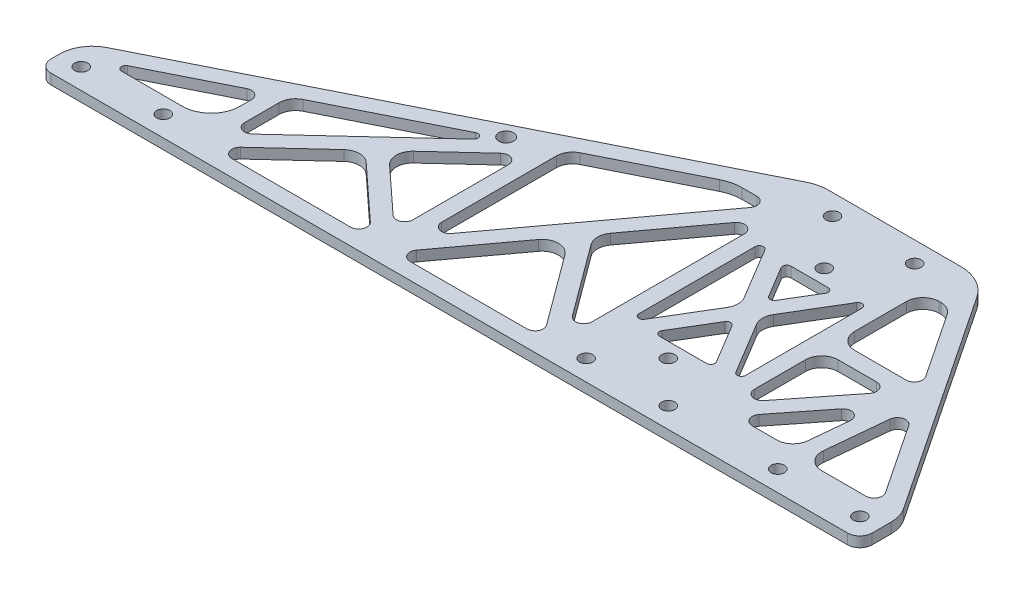
SolidWorks part; units mm, degrees
ref_plane "Front Plane" through (0, 0, 0) normal (0, 0, 1) x (1, 0, 0)
ref_plane "Top Plane" through (0, 0, 0) normal (0, 1, 0) x (1, 0, 0)
ref_plane "Right Plane" through (0, 0, 0) normal (1, 0, 0) x (0, 0, -1)
sketch "Sketch1" plane through (0, 0, 0) normal (0, 1, 0) x (1, 0, 0)
  line L0 (0, 0) -> (254, 0)
  line L2 (203.2, 88.9) -> (152.4, 88.9)
  line L4 (0, 0) -> (0, 12.7)
  line L5 (0, 12.7) -> (152.4, 88.9)
  line L6 (203.2, 88.9) -> (254, 12.7)
  line L7 (254, 12.7) -> (254, 0)
  line L8 (0, 6.35) -> (44.45, 6.35) construction
  line L9 (254, 6.35) -> (222.25, 6.35) construction
  line L10 (139.7, 82.55) -> (207.4333, 82.55) construction
  line L11 (44.45, 0) -> (44.45, 34.925) construction
  line L12 (156.6333, 12.7) -> (154.0933, 7.62)
  line L13 (224.7006, 47.4909) -> (221.314, 12.7) construction
  line L20 (127, 76.2) -> (211.6667, 76.2)
  line L21 (154.0933, 76.2) -> (101.6, 5.08) construction
  line L22 (154.0933, 12.7) -> (154.0933, 7.62)
  line L23 (247.8946, 12.7) -> (194.7333, 12.7)
  line L24 (224.7006, 47.4909) -> (197.2733, 12.7) construction
  line L28 (224.7006, 47.4909) -> (194.7333, 47.4909) construction
  line L31 (5.08, 9.5604) -> (153.5992, 83.82)
  line L32 (200.4813, 83.82) -> (153.5992, 83.82)
  line L33 (200.4813, 83.82) -> (248.92, 11.1619)
  line L34 (248.92, 11.1619) -> (248.92, 5.08)
  line L35 (5.08, 5.08) -> (248.92, 5.08)
  line L36 (5.08, 5.08) -> (5.08, 9.5604)
  line L37 (101.6, 5.08) -> (101.6, 57.8204) construction
  line L39 (127.8467, 40.64) -> (154.0933, 5.08) construction
  line L40 (101.6, 57.8204) -> (44.45, 5.08) construction
  line L41 (73.025, 31.4502) -> (101.6, 5.08) construction
  line L42 (154.0933, 7.62) -> (154.0933, 5.08)
  line L83 (152.8233, 5.08) -> (150.2833, 0)
  line L84 (125.803, 39.1316) -> (152.0497, 3.5716)
  line L107 (152.0497, 77.7084) -> (99.5564, 6.5884)
  line L108 (156.6333, 76.2) -> (194.7333, 12.7) construction
  line L113 (194.7333, 76.2) -> (156.6333, 12.7) construction
  line L117 (104.14, 5.08) -> (104.14, 63.6207)
  line L118 (156.6333, 12.7) -> (194.7333, 12.7)
  line L119 (194.7333, 12.7) -> (201.0833, 0)
  line L120 (154.0933, 6.35) -> (197.9083, 6.35) construction
  line L126 (192.5553, 77.5068) -> (154.4553, 14.0068)
  line L127 (154.4553, 74.8932) -> (192.5553, 11.3932)
  line L128 (156.6333, 12.7) -> (156.6333, 76.2) construction
  line L129 (194.7333, 12.7) -> (194.7333, 76.2) construction
  line L130 (197.2733, 12.7) -> (197.2733, 76.2)
  line L131 (159.1733, 12.7) -> (159.1733, 76.2)
  line L132 (192.1933, 12.7) -> (192.1933, 76.2)
  line L133 (154.0933, 12.7) -> (154.0933, 76.2)
  line L147 (196.9114, 74.8932) -> (158.8114, 11.3932)
  line L148 (158.8114, 77.5068) -> (196.9114, 14.0068)
  line L154 (104.14, 63.6207) -> (42.7274, 6.9466)
  line L155 (71.3024, 29.5836) -> (99.8774, 3.2134)
  line L156 (224.7006, 50.0309) -> (194.7333, 50.0309)
  line L157 (222.7059, 49.0635) -> (195.2786, 14.2725)
  line L158 (197.2733, 12.7) -> (197.2733, 7.62)
  line L159 (222.1726, 47.737) -> (218.7859, 12.9461)
  line L160 (129.8903, 42.1484) -> (156.137, 6.5884)
  line L163 (156.137, 74.6916) -> (103.6436, 3.5716)
  line L164 (99.06, 5.08) -> (99.06, 52.0201)
  line L165 (99.06, 52.0201) -> (46.1726, 3.2134)
  line L166 (175.6833, 19.05) -> (162.9833, 6.35) construction
  line L167 (175.6833, 19.05) -> (188.3833, 6.35) construction
  line L168 (162.9833, 82.55) -> (175.6833, 67.31) construction
  line L169 (175.6833, 67.31) -> (188.3833, 82.55) construction
  line L170 (161.6625, 21.082) -> (189.7041, 21.082) construction
  line L171 (161.6625, 23.622) -> (189.7041, 23.622)
  line L172 (163.1865, 65.278) -> (188.1801, 65.278) construction
  line L173 (163.1865, 62.738) -> (188.1801, 62.738)
  line L174 (74.7476, 33.3168) -> (103.3226, 6.9466)
  line L175 (224.7006, 44.9509) -> (194.7333, 44.9509)
  line L176 (226.6953, 45.9184) -> (199.268, 11.1275)
  line L177 (227.2287, 47.2449) -> (223.842, 12.4539)
  line L178 (8.8192, 11.43) -> (44.45, 11.43)
  line L179 (46.99, 0) -> (46.99, 34.925)
  line L180 (41.91, 0) -> (41.91, 34.925)
  line L181 (198.2745, 13.97) -> (221.4376, 13.97)
  circle A0 centre (6.7733, 6.35) radius 2.032
  circle A1 centre (32.1733, 6.35) radius 2.032
  circle A2 centre (222.25, 6.35) radius 2.032
  circle A3 centre (247.65, 6.35) radius 2.032
  circle A4 centre (162.9833, 82.55) radius 2.032
  circle A5 centre (188.3833, 82.55) radius 2.032
  circle A28 centre (162.9833, 6.35) radius 2.032
  circle A29 centre (188.3833, 6.35) radius 2.032
  arc A32 (197.2733, 12.7) -> (192.1933, 12.7) centre (194.7333, 12.7) cw
  arc A33 (197.2733, 76.2) -> (192.1933, 76.2) centre (194.7333, 76.2) ccw
  arc A34 (159.1733, 12.7) -> (154.0933, 12.7) centre (156.6333, 12.7) cw
  arc A35 (159.1733, 76.2) -> (154.0933, 76.2) centre (156.6333, 76.2) ccw
  arc A45 (192.5553, 77.5068) -> (196.9114, 74.8932) centre (194.7333, 76.2) cw
  arc A46 (154.4553, 14.0068) -> (158.8114, 11.3932) centre (156.6333, 12.7) ccw
  arc A47 (154.4553, 74.8932) -> (158.8114, 77.5068) centre (156.6333, 76.2) cw
  arc A48 (192.5553, 11.3932) -> (196.9114, 14.0068) centre (194.7333, 12.7) ccw
  circle A59 centre (175.6833, 19.05) radius 2.032
  circle A60 centre (175.6833, 67.31) radius 2.032
  arc A61 (125.803, 39.1316) -> (129.8903, 42.1484) centre (127.8467, 40.64) cw
  arc A62 (152.0497, 3.5716) -> (156.137, 6.5884) centre (154.0933, 5.08) ccw
  arc A63 (152.0497, 77.7084) -> (156.137, 74.6916) centre (154.0933, 76.2) cw
  arc A64 (99.5564, 6.5884) -> (103.6436, 3.5716) centre (101.6, 5.08) ccw
  arc A65 (104.14, 5.08) -> (99.06, 5.08) centre (101.6, 5.08) cw
  arc A66 (42.7274, 6.9466) -> (46.1726, 3.2134) centre (44.45, 5.08) ccw
  arc A67 (71.3024, 29.5836) -> (74.7476, 33.3168) centre (73.025, 31.4502) cw
  arc A68 (99.8774, 3.2134) -> (103.3226, 6.9466) centre (101.6, 5.08) ccw
  arc A69 (224.7006, 50.0309) -> (224.7006, 44.9509) centre (224.7006, 47.4909) cw
  arc A70 (194.7333, 50.0309) -> (194.7333, 44.9509) centre (194.7333, 47.4909) ccw
  arc A71 (222.7059, 49.0635) -> (226.6953, 45.9184) centre (224.7006, 47.4909) cw
  arc A72 (195.2786, 14.2725) -> (199.268, 11.1275) centre (197.2733, 12.7) ccw
  arc A73 (222.1726, 47.737) -> (227.2287, 47.2449) centre (224.7006, 47.4909) cw
  arc A74 (218.7859, 12.9461) -> (223.842, 12.4539) centre (221.314, 12.7) ccw
  arc A75 (46.99, 0) -> (41.91, 0) centre (44.45, 0) cw
  arc A76 (46.99, 34.925) -> (41.91, 34.925) centre (44.45, 34.925) ccw
  dimension "D7" = 4.064
  dimension "D8" = 25.4
  dimension "D9" = 130.81
  dimension "D10" = 25.4
  dimension "D11" = 6.35
  dimension "D13" = 19.05
  dimension "D1" = 254
  dimension "D2" = 50.8
  dimension "D3" = 88.9
  dimension "D4" = 152.4
  dimension "D5" = 12.7
  dimension "D6" = 6.35
  dimension "D12" = 25.4
  dimension "D14" = 44.45
  dimension "D15" = 12.7
  dimension "D16" = 57.15
  dimension "D18" = 12.7
  dimension "D19" = 2.54
  dimension "D20" = 50.8
  dimension "D21" = 25.4
  dimension "D22" = 2.54
  dimension "D23" = 6.35
  dimension "D24" = 2.54
  dimension "D29" = 6.35
  dimension "D30" = 38.1
  dimension "D31" = 25.4
  dimension "D32" = 6.35
  dimension "D33" = 2.54
  dimension "D36" = 12.7
  dimension "D38" = 15.24
  dimension "D39" = 2.54
  dimension "D40" = 2.54
  dimension "D27" = 1.27
  dimension "D17" = 5.08
  dimension "D25" = 2.54
  dimension "D26" = 2.54
  dimension "D37" = 2.54
extrude "Boss-Extrude1" add sketch "Sketch1" along normal blind 3.175 contours L0 L7 L6 L2 L5 L4 | A0 | A1 | A5 | A4 | A2 | A3
extrude "Cut-Extrude2" cut sketch "Sketch1<3>" along normal through all contours L154 L31 L11 | L155 L165 L35 | L165 L174 L164 | L117 L107 L20 L31 | L84 L163 L35 | L133 L163 L160 L22 | L157 L175 L130 | L156 L33 L20 L130 | L147 L148 L132 | L131 L126 L127 | L173 L148 L126 | L147 L171 L127 | L33 L177 L23 | L178 L180 L31 | L176 L181 L159 | A28 | A59 | A29 | A60 region at (30.8797, 0, -16.9451) region at (73.025, 0, -12.718) region at (62.4687, 0, -31.7097) region at (120.7695, 0, -51.2726) region at (127.8467, 0, -15.5076) region at (91.6301, 0, -31.4502) region at (206.5243, 0, -60.8789) region at (146.3968, 0, -40.64) region at (204.6702, 0, -35.5682) region at (175.6833, 0, -28.919) region at (187.6774, 0, -44.45) region at (213.9093, 0, -22.3524) region at (163.6893, 0, -44.45) region at (232.896, 0, -23.1836) region at (175.6833, 0, -58.2876)
sketch "Sketch1<3>" plane through (0, 0, 0) normal (0, 1, 0) x (1, 0, 0) same geometry as "Sketch1"
fillet "Fillet1" radius 3.81 2 edges at (254, 1.5875, 0) (0, 1.5875, 0)
fillet "Fillet2" radius 10.16 2 edges at (254, 1.5875, -12.7) (0, 1.5875, -12.7)
fillet "Fillet3" radius 12.7 2 edges at (203.2, 1.5875, -88.9) (152.4, 1.5875, -88.9)
fillet "Fillet4" radius 1.27 12 edges at (159.1733, 1.5875, -67.0298) (192.1933, 1.5875, -67.0298) (192.1933, 1.5875, -21.8702) (159.1733, 1.5875, -21.8702) (183.694, 1.5875, -62.738) (167.6727, 1.5875, -62.738) (175.6833, 1.5875, -49.3869) (185.218, 1.5875, -23.622) (166.1487, 1.5875, -23.622) (175.6833, 1.5875, -39.5131) (93.426, 1.5875, -53.7334) (8.8192, 1.5875, -11.43)
fillet "Fillet5" radius 2.54 19 edges at (223.0073, 1.5875, -50.0309) (247.8946, 1.5875, -12.7) (226.9275, 1.5875, -44.1507) (221.3335, 1.5875, -39.1171) (197.2733, 1.5875, -16.8027) (219.4639, 1.5875, -44.9509) (104.14, 1.5875, -12.7984) (99.06, 1.5875, -52.0201) (48.1953, 1.5875, -5.08) (97.8547, 1.5875, -5.08) (99.06, 1.5875, -10.8803) (104.7569, 1.5875, -5.08) (150.9364, 1.5875, -5.08) (154.0933, 1.5875, -9.3572) (154.0933, 1.5875, -71.9228) (150.9364, 1.5875, -76.2) (41.91, 1.5875, -27.9754) (46.99, 1.5875, -10.8803) (201.5089, 1.5875, -13.97)
fillet "Fillet6" radius 5.08 14 edges at (172.7212, 1.5875, -44.45) (178.6455, 1.5875, -44.45) (223.866, 1.5875, -12.7) (197.2733, 1.5875, -50.0309) (197.2733, 1.5875, -44.9509) (197.2733, 1.5875, -76.2) (205.5613, 1.5875, -76.2) (73.025, 1.5875, -27.9939) (76.7703, 1.5875, -31.4502) (104.14, 1.5875, -59.0904) (131.0036, 1.5875, -40.64) (127.8467, 1.5875, -36.3628) (46.99, 1.5875, -30.5154) (218.8856, 1.5875, -13.97)
fillet "Fillet7" radius 12.7 1 edges at (138.3592, 1.5875, -76.2)
fillet "Fillet10" radius 8.89 1 edges at (41.91, 1.5875, -11.43)
sketch "Sketch2" plane through (0, 3.175, 0) normal (0, 1, 0) x (1, 0, 0)
  line L0 (39.6875, 0) -> (39.6875, 8.89)
  line L1 (3.81, 0) -> (250.19, 0) construction
  line L2 (39.6875, 8.89) -> (49.2125, 8.89)
  line L3 (49.2125, 8.89) -> (49.2125, 0)
  line L4 (0, 3.81) -> (0, 6.4208) construction
  line L5 (202.2475, 0) -> (202.2475, 8.89)
  line L6 (202.2475, 8.89) -> (211.7725, 8.89)
  line L7 (211.7725, 8.89) -> (211.7725, 0)
  line L8 (254, 9.6238) -> (254, 3.81) construction
  line L9 (3.81, 0) -> (250.19, 0)
  dimension "D1" = 39.6875
  dimension "D2" = 9.525
  dimension "D3" = 8.89
  dimension "D4" = 42.2275
extrude "Cut-Extrude3" [suppressed] cut sketch "Sketch2" against normal through all contours L0 L9 L3 L2 | L5 L9 L7 L6
fillet "Fillet8" [suppressed] radius 1.27
fillet "Fillet9" [suppressed] radius 2.54
sketch "Sketch3" plane through (0, 3.175, 0) normal (0, 1, 0) x (1, 0, 0)
  line L0 (322.9659, 17.0563) -> (94.1827, 68.4886) construction
  circle A0 centre (322.9659, 17.0563) radius 2.286 construction
  circle A1 centre (322.9659, 17.0563) radius 2.286
  circle A2 centre (91.2882, 53.2846) radius 2.286
  arc A4 (94.1827, 68.4886) -> (88.6111, 9.0045) centre (322.9659, 17.0563) ccw construction
  dimension "D1" = 234.4931
  dimension "D2" = 4.572
extrude "Cut-Extrude4" cut sketch "Sketch3" against normal up to surface (3.175 mm away) contours A2 region at (91.2882, 3.175, -53.2846) up to face at (233.1564, 0, -22.5815)
